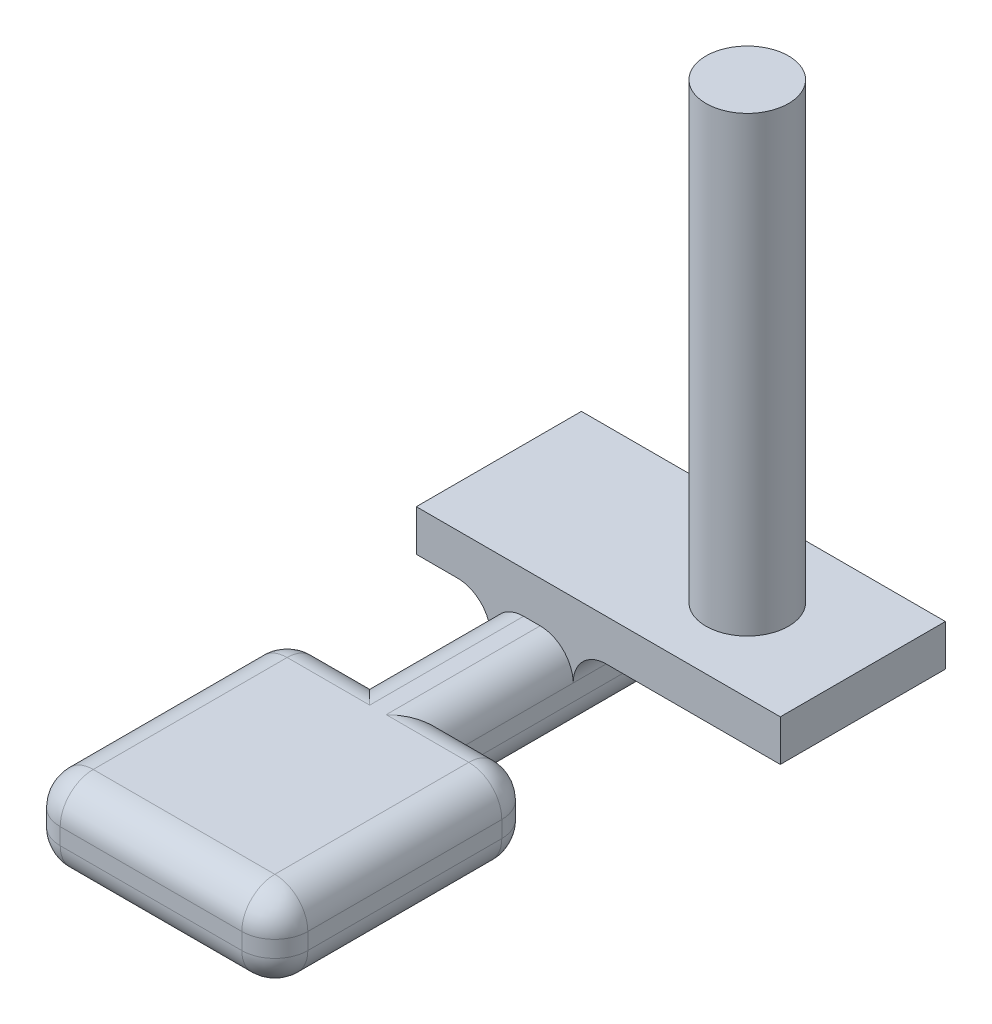
SolidWorks part; units mm, degrees
material "1060 Alloy"
ref_plane "Front Plane" through (0, 0, 0) normal (0, 0, 1) x (1, 0, 0)
ref_plane "Top Plane" through (0, 0, 0) normal (0, 1, 0) x (1, 0, 0)
ref_plane "Right Plane" through (0, 0, 0) normal (1, 0, 0) x (0, 0, -1)
sketch "Sketch1" plane through (0, 0, 0) normal (0, 1, 0) x (1, 0, 0)
  circle A0 centre (0, 0) radius 3.175
  dimension "D1" = 6.35
extrude "Boss-Extrude1" add sketch "Sketch1" along normal mid plane 38
sketch "Sketch2" plane through (0, -19, 0) normal (0, -1, 0) x (1, 0, 0)
  line L1 (-19.11, -6.35) -> (8.89, -6.35)
  line L2 (-19.11, -6.35) -> (-19.11, 6.35)
  line L3 (-19.11, 6.35) -> (8.89, 6.35)
  line L4 (8.89, -6.35) -> (8.89, 6.35)
  line L5 (-19.11, -6.35) -> (8.89, 6.35) construction
  line L6 (-19.11, 6.35) -> (8.89, -6.35) construction
  point P0 (-5.11, 0)
  dimension "D1" = 28
  dimension "D2" = 12.7
  dimension "D3" = 8.89
extrude "Boss-Extrude2" add sketch "Sketch2" against normal blind 3.175
sketch "Sketch3" plane through (0, -19, 0) normal (0, -1, 0) x (1, 0, 0)
  line L0 (-13.395, -6.35) -> (-13.395, 15.65)
  line L2 (-13.395, 15.65) -> (-19.745, 15.65)
  line L3 (-19.745, 15.65) -> (-19.745, 35.65)
  line L4 (-19.745, 35.65) -> (-0.695, 35.65)
  line L5 (-0.695, 35.65) -> (-0.695, 15.65)
  line L6 (-0.695, 15.65) -> (-7.045, 15.65)
  line L7 (-7.045, 15.65) -> (-7.045, -6.35)
  line L9 (-19.11, -6.35) -> (8.89, -6.35) construction
  line L11 (-13.395, -6.35) -> (-7.045, -6.35)
  line L12 (-19.11, 6.35) -> (-19.11, -6.35) construction
  point P2 (-10.22, -6.35)
  dimension "D1" = 42
  dimension "D2" = 20
  dimension "D3" = 8.89
  dimension "D4" = 6.35
  dimension "D5" = 19.05
extrude "Boss-Extrude3" add sketch "Sketch3" along normal blind 6.35
fillet "Fillet1" radius 2.54 21 edges at (-13.395, -25.35, 4.65) (-16.57, -25.35, 15.65) (-3.87, -25.35, 15.65) (-7.045, -25.35, 4.65) (-10.22, -25.35, -6.35) (-0.695, -22.175, 15.65) (-0.695, -25.35, 25.65) (-0.695, -19, 25.65) (-0.695, -22.175, 35.65) (-10.22, -25.35, 35.65) (-10.22, -19, 35.65) (-19.745, -22.175, 35.65) (-19.745, -25.35, 25.65) (-19.745, -22.175, 15.65) (-19.745, -19, 25.65) (-3.87, -19, 15.65) (-16.57, -19, 15.65) (-7.045, -19, 11) (-13.395, -19, 11) (-7.045, -22.175, -6.35) (-13.395, -22.175, -6.35)
fillet "Fillet2" radius 2.54 4 edges at (-7.7889, -19, -5.6061) (-12.6511, -19, -5.6061) (-7.045, -19, 1.27) (-13.395, -19, 1.27)
